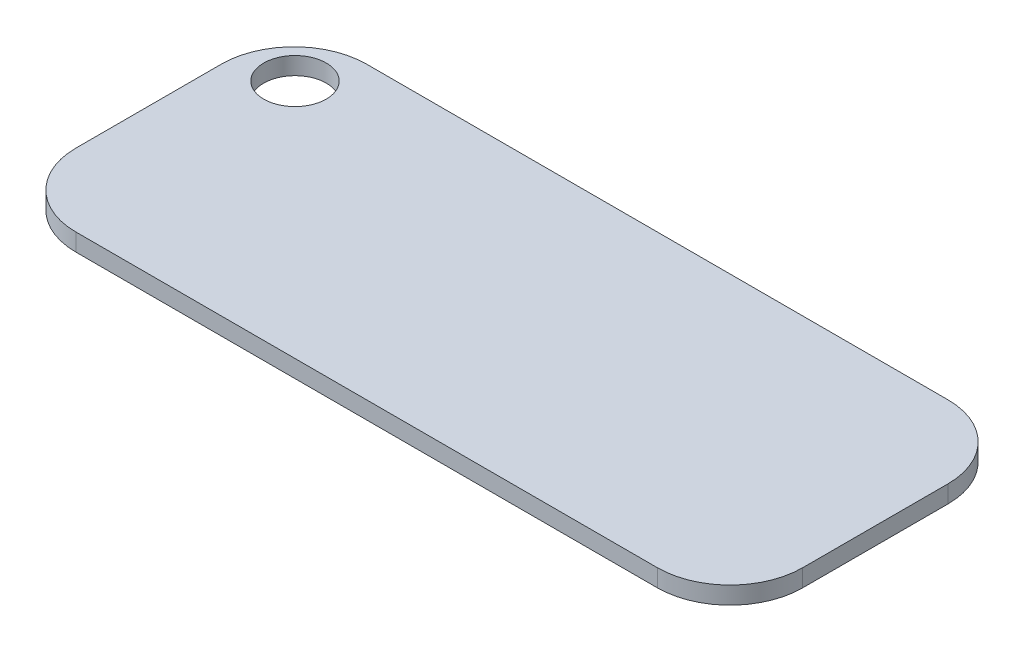
SolidWorks part; units mm, degrees
ref_plane "Спереди" through (0, 0, 0) normal (0, 0, 1) x (1, 0, 0)
ref_plane "Сверху" through (0, 0, 0) normal (0, 1, 0) x (1, 0, 0)
ref_plane "Справа" through (0, 0, 0) normal (1, 0, 0) x (0, 0, -1)
other "Configuration Table"
sketch "Эскиз1" plane through (0, 0, 0) normal (0, 1, 0) x (1, 0, 0)
  line L1 (0, 0) -> (50, 0)
  line L2 (0, 0) -> (0, 20)
  line L3 (0, 20) -> (50, 20)
  line L4 (50, 0) -> (50, 20)
  dimension "D1" = 20
  dimension "D2" = 50
extrude "Бобышка-Вытянуть1" add sketch "Эскиз1" along normal blind 1.2 contours L2 L3 L4 L1
fillet "Скругление1" radius 5 1 edges at (0, 0.6, -20)
fillet "Скругление2" radius 5 1 edges at (0, 0.6, 0)
fillet "Скругление3" radius 5 1 edges at (50, 0.6, -20)
fillet "Скругление4" radius 5 1 edges at (50, 0.6, 0)
sketch "Эскиз4" plane through (0, 1.2, 0) normal (0, 1, 0) x (1, 0, 0)
  circle A0 centre (3.5425, 16.5284) radius 2.1519
extrude "Вырез-Вытянуть1" cut sketch "Эскиз4" against normal blind 3
sketch "Эскиз5" plane through (0, 0, 0) normal (0, -1, 0) x (1, 0, 0)
  line L0 (0.0184, -14.5717) -> (50.4167, -14.5717) construction
  arc A0 (0, -15) -> (5, -20) centre (5, -15) ccw construction
  text T0 "<b>  89109002895</b>" font "@Adobe Gothic Std B" height 10
  point P3 (0, -15.2234)
  point P4 (0, -13.3901)
  point P5 (0, 0)
  point P6 (0, 0)
  point P7 (0, -14.5717)
extrude "надпись" add sketch "Эскиз5" along normal blind 1.2
